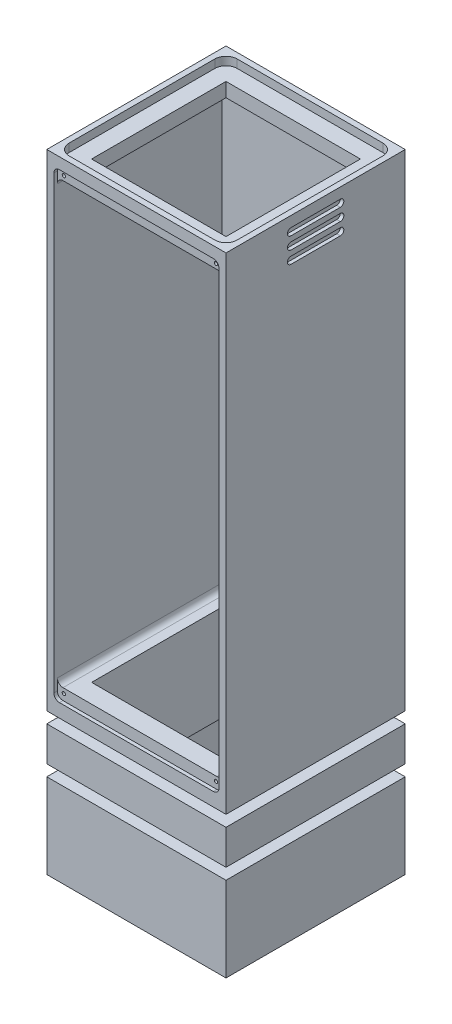
SolidWorks part; units mm, degrees
ref_plane "Front Plane" through (0, 0, 0) normal (0, 0, 1) x (1, 0, 0)
ref_plane "Top Plane" through (0, 0, 0) normal (0, 1, 0) x (1, 0, 0)
ref_plane "Right Plane" through (0, 0, 0) normal (1, 0, 0) x (0, 0, -1)
sketch "Sketch1" plane through (0, 0, 0) normal (0, 1, 0) x (1, 0, 0)
  line L0 (6.35, 44.45) -> (44.45, 44.45)
  line L1 (0, 0) -> (50.8, 0)
  line L2 (0, 0) -> (0, 50.8)
  line L3 (0, 50.8) -> (50.8, 50.8)
  line L4 (50.8, 0) -> (50.8, 50.8)
  line L5 (44.45, 6.35) -> (44.45, 44.45)
  line L6 (6.35, 6.35) -> (44.45, 6.35)
  line L7 (6.35, 6.35) -> (6.35, 44.45)
  dimension "D1" = 50.8
  dimension "D2" = 6.35
extrude "Boss-Extrude1" add sketch "Sketch1" along normal blind 178
sketch "Sketch2" plane through (0, 0, 0) normal (0, -1, 0) x (1, 0, 0)
  line L0 (47.8, -3) -> (3, -3)
  line L1 (3, -3) -> (3, -47.8)
  line L2 (3, -47.8) -> (47.8, -47.8)
  line L3 (47.8, -47.8) -> (47.8, -3)
  line L4 (6.35, -44.45) -> (44.45, -44.45)
  line L5 (6.35, -6.35) -> (6.35, -44.45)
  line L6 (44.45, -6.35) -> (6.35, -6.35)
  line L7 (44.45, -44.45) -> (44.45, -6.35)
  line L8 (6.35, -44.45) -> (44.45, -44.45)
  line L9 (6.35, -6.35) -> (6.35, -44.45)
  line L10 (44.45, -6.35) -> (6.35, -6.35)
  line L11 (44.45, -44.45) -> (44.45, -6.35)
  line L12 (0, -50.8) -> (0, 0) construction
  dimension "D2" = 3
  dimension "D1" = 0
extrude "Cut-Extrude1" cut sketch "Sketch2" against normal blind 20
sketch "Sketch3" plane through (0, 0, 0) normal (0, 0, 1) x (1, 0, 0)
  line L0 (0, 0) -> (50.8, 0) construction
  line L1 (2, 171.65) -> (48.8, 171.65)
  line L2 (2, 171.65) -> (2, 47.175)
  line L3 (2, 47.175) -> (48.8, 47.175)
  line L4 (48.8, 171.65) -> (48.8, 47.175)
  line L5 (0, 178) -> (0, 0) construction
  line L6 (50.8, 178) -> (50.8, 0) construction
  line L7 (0, 178) -> (50.8, 178) construction
  dimension "D1" = 47.175
  dimension "D2" = 2
  dimension "D3" = 2
  dimension "D4" = 6.35
extrude "Cut-Extrude2" cut sketch "Sketch3" against normal blind 47.625
sketch "Sketch4" plane through (0, 0, 0) normal (0, 0, 1) x (1, 0, 0)
  line L0 (0, 178) -> (0, 0) construction
  line L1 (0, 27.175) -> (50.8, 27.175)
  line L2 (0, 27.175) -> (0, 24)
  line L3 (0, 24) -> (50.8, 24)
  line L4 (50.8, 27.175) -> (50.8, 24)
  line L5 (50.8, 178) -> (50.8, 0) construction
  line L6 (0, 0) -> (50.8, 0) construction
  line L8 (0, 37) -> (50.8, 37)
  line L9 (0, 37) -> (0, 40.175)
  line L10 (0, 40.175) -> (50.8, 40.175)
  line L11 (50.8, 37) -> (50.8, 40.175)
  dimension "D1" = 24
  dimension "D2" = 3.175
  dimension "D3" = 13
extrude "Cut-Extrude3" cut sketch "Sketch4" against normal blind 3.175
sketch "Sketch5" plane through (0, 0, 0) normal (0, 0, 1) x (1, 0, 0)
  line L0 (50.8, 40.175) -> (0, 40.175) construction
  line L1 (0, 37) -> (3.175, 37)
  line L2 (0, 37) -> (0, 40.175)
  line L3 (0, 40.175) -> (3.175, 40.175)
  line L4 (3.175, 37) -> (3.175, 40.175)
  line L5 (0, 24) -> (50.8, 24) construction
  line L6 (0, 27.175) -> (3.175, 27.175)
  line L7 (0, 27.175) -> (0, 24)
  line L8 (0, 24) -> (3.175, 24)
  line L9 (3.175, 27.175) -> (3.175, 24)
  dimension "D1" = 3.175
extrude "Cut-Extrude4" cut sketch "Sketch5" against normal through all
ref_plane "Plane1" through (0, 0, -25.4) normal (0, 0, 1) x (1, 0, 0)
ref_plane "Plane2" through (25.4, 0, 0) normal (-1, 0, 0) x (0, 0, 1)
sketch "Sketch6" plane through (0, 0, 0) normal (-1, 0, 0) x (0, 0, 1)
  line L0 (-32.4, 174) -> (-18.4, 174) construction
  line L1 (-32.4, 175) -> (-18.4, 175)
  line L2 (-32.4, 173) -> (-18.4, 173)
  line L3 (-32.4, 170.5) -> (-18.4, 170.5) construction
  line L4 (-32.4, 171.5) -> (-18.4, 171.5)
  line L5 (-32.4, 169.5) -> (-18.4, 169.5)
  line L6 (-32.4, 167) -> (-18.4, 167) construction
  line L9 (-32.4, 168) -> (-18.4, 168)
  line L10 (-32.4, 166) -> (-18.4, 166)
  line L11 (-25.4, 174) -> (-25.4, 170.5) construction
  line L12 (-25.4, 170.5) -> (-25.4, 167) construction
  line L13 (-25.4, 174) -> (-25.4, 178) construction
  line L14 (-50.8, 178) -> (0, 178) construction
  arc A0 (-32.4, 175) -> (-32.4, 173) centre (-32.4, 174) ccw
  arc A1 (-18.4, 173) -> (-18.4, 175) centre (-18.4, 174) ccw
  arc A2 (-32.4, 171.5) -> (-32.4, 169.5) centre (-32.4, 170.5) ccw
  arc A3 (-18.4, 169.5) -> (-18.4, 171.5) centre (-18.4, 170.5) ccw
  arc A6 (-32.4, 168) -> (-32.4, 166) centre (-32.4, 167) ccw
  arc A7 (-18.4, 166) -> (-18.4, 168) centre (-18.4, 167) ccw
  point P2 (-25.4, 174)
  point P9 (-25.4, 170.5)
  point P16 (-25.4, 167)
  point P25 (-33.4, 167)
  point P26 (-17.4, 167)
  dimension "D1" = 3.5
  dimension "D2" = 2
  dimension "D3" = 4
  dimension "D4" = 16
extrude "Cut-Extrude5" cut sketch "Sketch6" against normal blind 1
mirror "Mirror1" about plane through (0, 0, -25.4) normal (0, 0, 1) of "Cut-Extrude3"
mirror "Mirror2" about plane through (25.4, 0, 0) normal (-1, 0, 0) of "Cut-Extrude5", "Cut-Extrude4"
sketch "Sketch7" plane through (0, 0, 0) normal (0, 0, 1) x (1, 0, 0)
  line L0 (0, 178) -> (50.8, 178) construction
  line L1 (2, 171.65) -> (48.8, 171.65)
  line L2 (2, 171.65) -> (2, 174.825)
  line L3 (2, 174.825) -> (48.8, 174.825)
  line L4 (48.8, 171.65) -> (48.8, 174.825)
  line L6 (2, 47.175) -> (48.8, 47.175)
  line L7 (2, 47.175) -> (2, 44)
  line L8 (2, 44) -> (48.8, 44)
  line L9 (48.8, 47.175) -> (48.8, 44)
  dimension "D1" = 3.175
extrude "Cut-Extrude6" cut sketch "Sketch7" against normal blind 1
fillet "Fillet1" radius 1.5875 12 edges at (47.8, 10, -47.8) (47.8, 10, -3) (3, 10, -47.8) (3, 10, -3) (48.8, 47.175, -24.3125) (2, 47.175, -24.3125) (48.8, 171.65, -24.3125) (2, 171.65, -24.3125) (48.8, 174.825, -0.5) (2, 174.825, -0.5) (48.8, 44, -0.5) (2, 44, -0.5)
sketch "Sketch8" plane through (0, 178, 0) normal (0, 1, 0) x (1, 0, 0)
  line L0 (0, 50.8) -> (0, 0) construction
  line L1 (4.7625, 49.2125) -> (46.0375, 49.2125)
  line L2 (1.5875, 46.0375) -> (1.5875, 4.7625)
  line L3 (4.7625, 1.5875) -> (46.0375, 1.5875)
  line L4 (49.2125, 46.0375) -> (49.2125, 4.7625)
  line L5 (50.8, 50.8) -> (0, 50.8) construction
  line L6 (0, 0) -> (50.8, 0) construction
  arc A0 (46.0375, 49.2125) -> (49.2125, 46.0375) centre (46.0375, 46.0375) cw
  arc A1 (49.2125, 4.7625) -> (46.0375, 1.5875) centre (46.0375, 4.7625) cw
  arc A2 (4.7625, 1.5875) -> (1.5875, 4.7625) centre (4.7625, 4.7625) cw
  arc A3 (1.5875, 46.0375) -> (4.7625, 49.2125) centre (4.7625, 46.0375) cw
  dimension "D1" = 3.175
  dimension "D2" = 1.5875
  dimension "D3" = 1.5875
  dimension "D4" = 1.5875
extrude "Cut-Extrude7" cut sketch "Sketch8" against normal blind 2.3444
hole_wizard "M1.2x0.25 Tapped Hole1" positions "Sketch12" profile "Sketch14" tap size "M1.2x0.25" standard "ANSI Metric"
sketch "Sketch12" plane through (0, 0, -1) normal (0, 0, 1) x (1, 0, 0)
  line L0 (2, 48.7625) -> (2, 45.5875) construction
  line L1 (3.5875, 44) -> (47.2125, 44) construction
  line L2 (3.8415, 172.9838) -> (3.8415, 45.8415) construction
  line L3 (3.8415, 45.8415) -> (46.9588, 45.8415) construction
  line L4 (46.9588, 45.8415) -> (46.9588, 172.9838) construction
  line L5 (46.9588, 172.9838) -> (3.8415, 172.9838) construction
  line L6 (47.2125, 174.825) -> (3.5875, 174.825) construction
  line L7 (48.8, 45.5875) -> (48.8, 173.2375) construction
  point P0 (3.8415, 172.9838)
  point P3 (46.9588, 172.9838)
  point P6 (3.8415, 45.8415)
  point P9 (46.9588, 45.8415)
  point P29 (46.0803, 46.2876)
  point P30 (47.2125, 45.5875)
  point P31 (45.7631, 46.0611)
  dimension "D1" = 1.8415
  dimension "D2" = 1.8415
  dimension "D3" = 1.8412
  dimension "D4" = 1.8412
sketch "Sketch14" plane through (3.8415, 172.9838, -1) normal (1, 0, 0) x (0, -1, 0)
  line L0 (0, 0) -> (0, 3.2851)
  line L1 (0, 3.2851) -> (0.475, 2.9997)
  line L2 (0.475, 2.9997) -> (0.475, 0)
  line L5 (0.475, 0) -> (0, 0)
  line L10 (0, 3.2851) -> (-0.475, 2.9997) construction
  line L11 (0, -6.35) -> (0, 107.95) construction
  dimension "Tap Drill Dia." = 0.95
  dimension "Tap Drill Depth" = 2.9997
  dimension "Drill Angle" = 118
cosmetic thread "Hole Thread5" parameters "D1"=2.4, "D2"=1.2
cosmetic thread "Hole Thread6" parameters "D1"=2.4, "D2"=1.2
cosmetic thread "Hole Thread7" parameters "D1"=2.4, "D2"=1.2
cosmetic thread "Hole Thread8" parameters "D1"=2.4, "D2"=1.2
